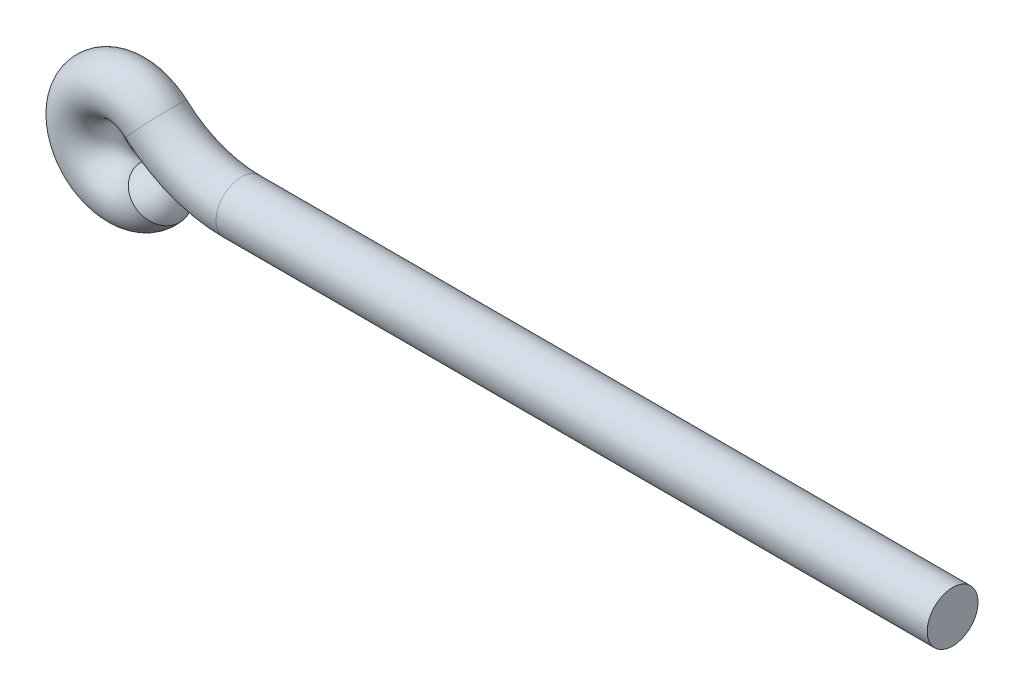
SolidWorks part; units mm, degrees
ref_plane "Front Plane" through (0, 0, 0) normal (0, 0, 1) x (1, 0, 0)
ref_plane "Top Plane" through (0, 0, 0) normal (0, 1, 0) x (1, 0, 0)
ref_plane "Right Plane" through (0, 0, 0) normal (1, 0, 0) x (0, 0, -1)
sketch "Sketch40" plane through (0, 0, 0) normal (0, 0, 1) x (1, 0, 0)
  line L0 (0, 0) -> (2.2225, 0) construction
  line L1 (0, 0) -> (1.7025, -1.4286) construction
  line L2 (5.7589, 0) -> (10.8389, 0)
  arc A1 (1.4931, 1.6463) -> (1.7025, -1.4286) centre (0, 0) ccw
  arc A2 (1.4931, 1.6463) -> (5.7589, 0) centre (5.7589, 6.35) ccw
  dimension "D1" = 4.445
  dimension "D4" = 6.35
  dimension "D2" = 40
  dimension "D3" = 5.08
sweep "Sweep3" add path "Sketch40" circular profile diameter 2.54 parameters "D3"=2.54
dome "Dome1" faces to dome 1 distance 0.889 reverse direction no elliptical dome no face at (1.7025, -1.4286, 1.27) parameters "D1"=0.889
sketch "Sketch61" plane through (10.8389, 0, 0) normal (1, 0, 0) x (0, 0, -1)
  circle A1 centre (0, 0) radius 1.27
  circle A2 centre (0, 0) radius 1.27
  dimension "D1" = 0
extrude "Boss-Extrude2" add sketch "Sketch61" along normal blind 30.48
scale "Scale1" scale about centroid uniform scaling yes scale factor 12.375
